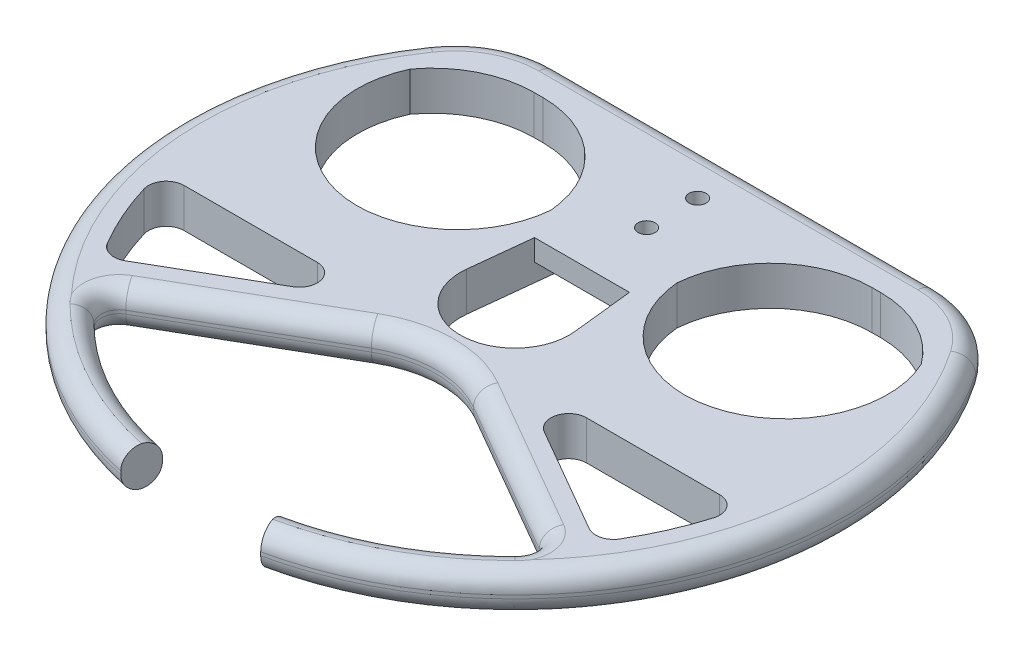
SolidWorks part; units mm, degrees
ref_plane "Front Plane" through (0, 0, 0) normal (0, 0, 1) x (1, 0, 0)
ref_plane "Top Plane" through (0, 0, 0) normal (0, 1, 0) x (1, 0, 0)
ref_plane "Right Plane" through (0, 0, 0) normal (1, 0, 0) x (0, 0, -1)
sketch "Sketch1" plane through (0, 0, 0) normal (0, 1, 0) x (1, 0, 0)
  line L0 (6.3626, 0.691) -> (3.9766, 22.6618)
  line L1 (-6.3626, 0.691) -> (-3.9766, 22.6618)
  line L2 (0, 27.2299) -> (-27.9201, 27.2299)
  line L3 (0, 27.2299) -> (27.9201, 27.2299)
  line L4 (-6.3626, 0.691) -> (-34.9932, 0.691)
  line L5 (6.3626, 0.691) -> (34.9932, 0.691)
  line L6 (-7.3677, 22.6618) -> (-26.6729, 22.6618)
  line L7 (7.3677, 22.6618) -> (26.6729, 22.6618)
  line L10 (0, -7.4) -> (-7.1951, -34.2525) construction
  line L11 (0, -7.4) -> (0, -34.2525) construction
  line L12 (-7.1951, -34.2525) -> (-8.2318, -38.1214)
  line L13 (7.1951, -34.2525) -> (8.2318, -38.1214)
  line L14 (0, -7.4) -> (7.1951, -34.2525) construction
  line L15 (-34.2088, -7.4) -> (0, -7.4)
  line L16 (0, -7.4) -> (34.2088, -7.4)
  line L17 (0, 26.2299) -> (0, 27.2299) construction
  line L18 (-5.5797, 7.9) -> (5.5797, 7.9)
  line L19 (0, 21.5) -> (0, 15.5) construction
  line L20 (0, 15.5) -> (0, 7.9) construction
  line L21 (-7.3677, 0.691) -> (-7.3677, 22.6618)
  line L22 (7.3677, 0.691) -> (7.3677, 22.6618)
  line L23 (0, -7.4) -> (-26.5942, -22.7541)
  line L24 (-8, -7.4) -> (-29.0347, -19.5444)
  line L25 (0, -7.4) -> (26.5942, -22.7541)
  line L26 (8, -7.4) -> (29.0347, -19.5444)
  circle A0 centre (0, 0) radius 40 construction
  arc A1 (-27.9201, 27.2299) -> (-8.2318, -38.1214) centre (0, 0) ccw
  arc A2 (-6.3626, 0.691) -> (6.3626, 0.691) centre (0, 0) ccw
  arc A3 (3.9766, 22.6618) -> (-3.9766, 22.6618) centre (0, 22.2299) ccw
  arc A4 (-26.6729, 22.6618) -> (-34.9932, 0.691) centre (0, 0) ccw
  arc A5 (-34.2088, -7.4) -> (-7.1951, -34.2525) centre (0, 0) ccw
  arc A6 (34.9932, 0.691) -> (26.6729, 22.6618) centre (0, 0) ccw
  arc A7 (8.2318, -38.1214) -> (27.9201, 27.2299) centre (0, 0) ccw
  arc A8 (7.1951, -34.2525) -> (34.2088, -7.4) centre (0, 0) ccw
  arc A9 (-7.3677, 0.691) -> (7.3677, 0.691) centre (0, 0) ccw construction
  arc A10 (-7.3567, 0.7989) -> (7.3567, 0.7989) centre (0, 0) ccw construction
  circle A11 centre (0, 15.5) radius 1
  circle A12 centre (0, 21.5) radius 1
  dimension "D1" = 80
  dimension "D2" = 78
  dimension "D4" = 8
  dimension "D5" = 12.8
  dimension "D6" = 70
  dimension "D11" = 2
  dimension "D12" = 2
  dimension "D3" = 22.1
  dimension "D7" = 30
  dimension "D9" = 1
  dimension "D13" = 6
  dimension "D10" = 7.9
  dimension "D14" = 7.6
  dimension "D15" = 60
  dimension "D16" = 4
  dimension "D8" = 1
extrude "Boss-Extrude1" add sketch "Sketch1" along normal blind 2.5 contours A8 L13 A7 L3 L2 A1 L12 A5 L15 L16 A6 L5 A2 L4 A4 L6 L21 L1 A3 L0 L22 L7 | L0 A3 L1 L18 A12 A11 | L24 A5 L23 L15 | L25 A8 L26 L16 region at (0, 0, -8.1146) region at (13.96, 0, -26.2123) region at (-15.8227, 0, 14.3156) region at (15.8227, 0, 14.3156)
extrude "Boss-Extrude3" add sketch "Sketch1<4>" against normal blind 2.1 contours A8 L13 A7 L3 L2 A1 L12 A5 L15 L16 A6 L5 A2 L4 A4 L6 A3 L7 | L25 A8 L26 L16 | L24 A5 L23 L15 region at (13.96, 0, -26.2123) region at (-15.8227, 0, 14.3156) region at (15.8227, 0, 14.3156)
sketch "Sketch1<4>" plane through (0, 0, 0) normal (0, 1, 0) x (1, 0, 0) same geometry as "Sketch1"
fillet "Fillet1" radius 12 11 edges at (26.6729, 0.2, -22.6618) (-26.6729, 0.2, -22.6618) (34.9932, 0.2, -0.691) (27.9201, 0.2, -27.2299) (-27.9201, 0.2, -27.2299) (-34.9932, 0.2, -0.691) (0, 0.2, 7.4) (7.3677, 0.2, -22.6618) (7.3677, 0.2, -0.691) (-7.3677, 0.2, -0.691) (-7.3677, 0.2, -22.6618)
fillet "Fillet2" radius 2.1 23 edges at (36.2265, -2.1, 14.4445) (27.897, -2.1, -25.8419) (0, -2.1, -27.2299) (-27.897, -2.1, -25.8419) (17.846, 2.5, 30.1085) (36.2265, 2.5, 14.4445) (27.897, 2.5, -25.8419) (0, 2.5, -27.2299) (-27.897, 2.5, -25.8419) (-36.2265, -2.1, 14.4445) (-17.846, 2.5, 30.1085) (-36.2265, 2.5, 14.4445) (16.2971, 2.5, 16.8091) (0, 2.5, 9.2564) (-16.2971, 2.5, 16.8091) (-8, 0.2, 7.4) (-34.2088, 0.2, 7.4) (-29.0347, 0.2, 19.5444) (34.2088, 0.2, 7.4) (29.0347, 0.2, 19.5444) (8, 0.2, 7.4) (26.5942, 0.2, 22.7541) (-26.5942, 0.2, 22.7541)
fillet "Fillet3" radius 2.1 7 edges at (16.667, -2.1, 30.7768) (25.3506, -2.1, 22.9847) (15.1593, -2.1, 16.1522) (-16.667, -2.1, 30.7768) (-25.3506, -2.1, 22.9847) (-15.1593, -2.1, 16.1522) (0, -2.1, 9.2564)
equation "\"D12@Sketch1\"=\"D11@Sketch1\""
equation "\"D6@Sketch1\"=\"D2@Sketch1\"-8"
